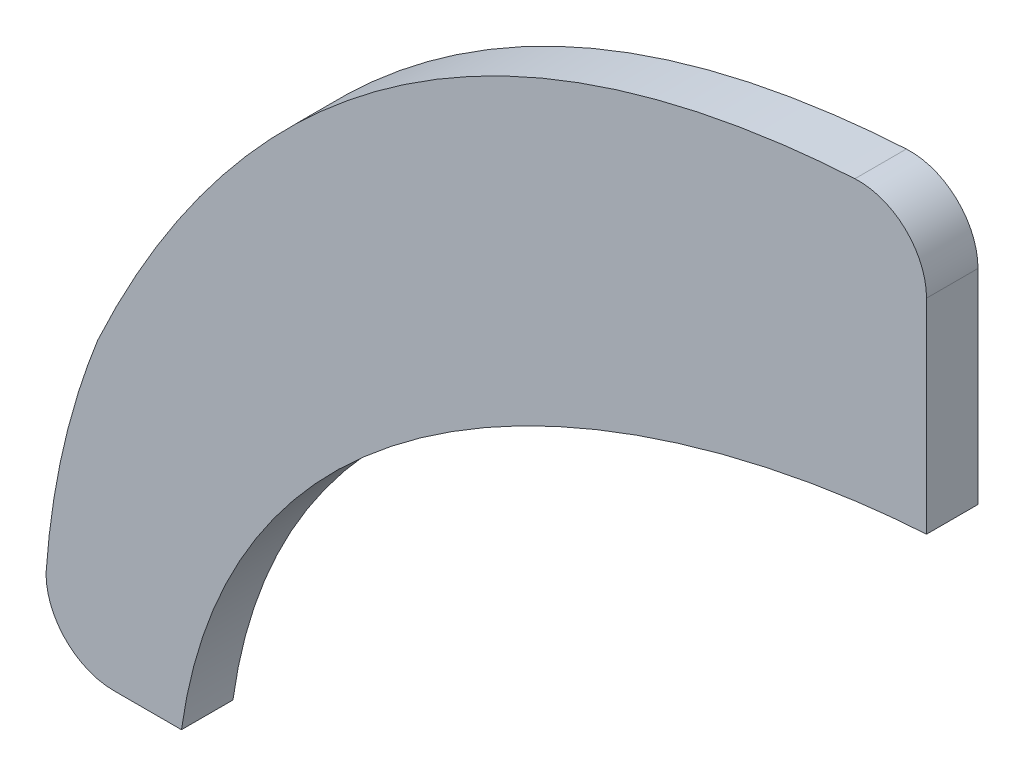
SolidWorks part; units mm, degrees
ref_plane "Front Plane" through (0, 0, 0) normal (0, 0, 1) x (1, 0, 0)
ref_plane "Top Plane" through (0, 0, 0) normal (0, 1, 0) x (1, 0, 0)
ref_plane "Right Plane" through (0, 0, 0) normal (1, 0, 0) x (0, 0, -1)
sketch "Sketch1" plane through (0, 0, 0) normal (0, 0, 1) x (1, 0, 0)
  line L0 (82.55, 69.9651) -> (82.55, 57.15)
  line L1 (6.35, 0) -> (82.55, 0)
  line L2 (0, 6.35) -> (0, 63.5)
  line L3 (0, 63.5) -> (76.2, 63.5)
  line L4 (82.55, 0) -> (82.55, 57.15)
  line L5 (41.7127, 63.5) -> (76.2, 63.5)
  arc A1 (0, 6.35) -> (6.35, 0) centre (6.35, 6.35) ccw
  arc A2 (82.55, 69.9651) -> (75.8341, 76.3045) centre (76.2, 69.9651) ccw
  spline S0 degree 2 poles (0, 6.35) (0.7728, 17.4696) (4.8742, 27.7603) knots 0 0 0 1 1 1
  spline S1 degree 3 poles (12.7, 0) (17.2635, 32.9464) (53.3334, 49.0332) (82.55, 50.8) knots 0 0 0 0 1 1 1 1
  spline S2 degree 3 poles (4.8742, 27.7603) (18.8154, 57.8764) (43.0066, 74.41) (75.8341, 76.3045) knots 0 0 0 0 0.937259 0.937259 0.937259 0.937259
  point P7 (82.55, 63.5)
  point P10 (0, 0)
  dimension "D4" = 12.7
  dimension "D6" = 6.35
  dimension "D1" = 82.55
  dimension "D2" = 63.5
  dimension "D5" = 12.7
extrude "Boss-Extrude1" add sketch "Sketch1" along normal blind 4.826 contours L1 S1 L4 L3 L2 A1 region at (40.0162, 45.9754, 0)
equation "\"MDF\"= 0.19in"
equation "\"PVCID\" = 2.067in"
equation "\"PVCOD\" = 2.375in"
equation "\"GenDiameter\"= 60mm"
equation "\"GenCutDiameter\" = 1.8in"
equation "\"GenCutDistance\" = 1"
equation "\"TowerHeight\" = 6in"
equation "\"TowerFrontBase\" = 3in"
equation "\"FunnelHeight\" = 1in"
equation "\"FunnelAngle\" = 20"
equation "\"TowerSideBase\" = 3in"
equation "\"TowerPanelLength\" = 2in"
equation "\"TowerPanelLeeway\" = 0.5in"
equation "\"BaseLength\" = 9in"
equation "\"BaseWidth\" = 10in"
equation "\"WheelHoleLength\" = 3.25in"
equation "\"WheelHoleWidth\" = 26mm"
equation "\"WheelHoleFromBack\" = 1.5in"
equation "\"DropLength\" = 1in"
equation "\"DropWidth\" = 8.5in"
equation "\"BumperWidth\" = 2in"
equation "\"SmallHexDiameter\" = 0.185in"
equation "\"SmallHexHeight\" = 0.701in"
equation "\"ScrewSize\" = 0.106in"
equation "\"BigHexDiameter\" = 0.251in"
equation "\"BigHexHeight\" = 0.374in"
equation "\"PCBThickness\" = 0.066in"
equation "\"ConnectorHeight\" = 0.517in"
equation "\"BoardHeight\" = 0.583in"
equation "\"UnoStackHeight\" = 1.351in"
equation "\"UnoStackWidth\" = 3.053in"
equation "\"UnoStackLength\" = 3.152in"
equation "\"HBridgeWidth\" = 1.797in"
equation "\"HBridgeLength\" = 2.236in"
equation "\"DSWidth\" = 1.820in"
equation "\"DSLength\" = 1.833in"
equation "\"StepperWidth\" = 1.799in"
equation "\"StepperLength\" = 2.248in"
equation "\"ULNWidth\" = 1.304in"
equation "\"ULNLength\" = 1.545in"
equation "\"VSwitchHeight\" = 0.392in"
equation "\"VSwitchWidth\" = 0.637in"
equation "\"VSwitchLength\" = 1.097in"
equation "\"SkateWheelDiameter\" = 80mm"
equation "\"SkateWheelThickness\" = 24mm"
equation "\"BaseDistance\" = 3in"
equation "\"DummyVar\" = 2in"
equation "\"D1@Boss-Extrude1\"=\"MDF\""
